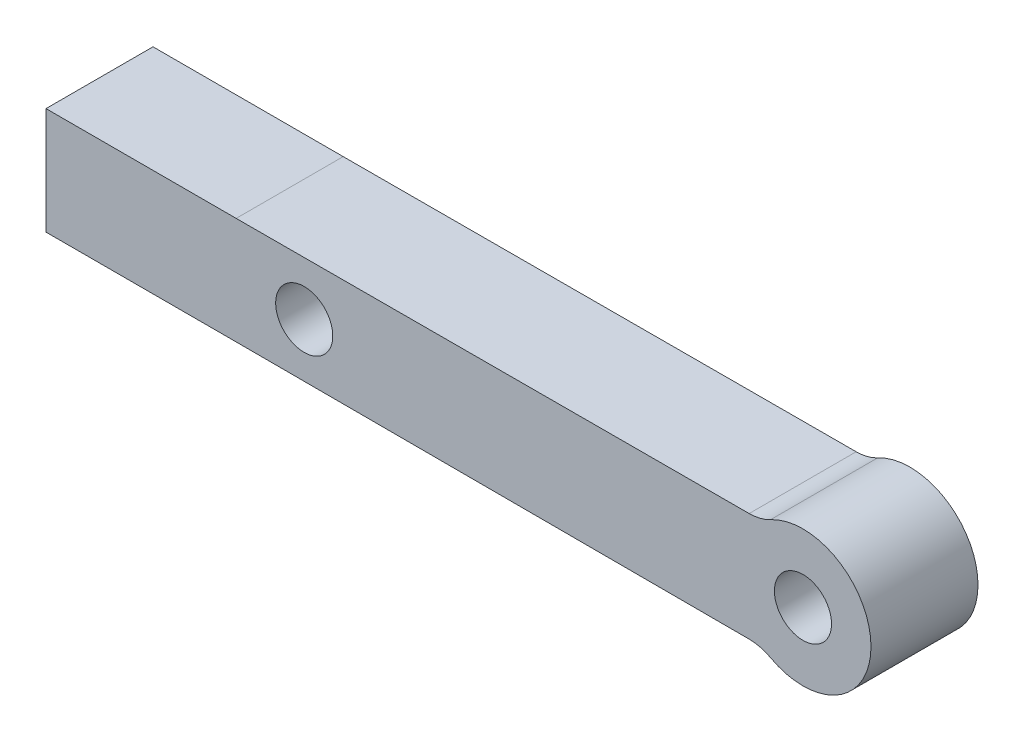
SolidWorks part; units mm, degrees
ref_plane "Front Plane" through (0, 0, 0) normal (0, 0, 1) x (1, 0, 0)
ref_plane "Top Plane" through (0, 0, 0) normal (0, 1, 0) x (1, 0, 0)
ref_plane "Right Plane" through (0, 0, 0) normal (1, 0, 0) x (0, 0, -1)
sketch "Sketch1" plane through (0, 0, 0) normal (0, 0, 1) x (1, 0, 0)
  line L0 (-31.75, 2.9972) -> (-37.7444, 2.9972)
  line L1 (-37.7444, 2.9972) -> (-42.4037, 2.9972)
  line L2 (-31.75, 2.9972) -> (-3.014, 3.0467)
  line L3 (-42.4037, 2.9972) -> (-42.4037, -2.9972)
  line L4 (-31.75, -2.9972) -> (-3.014, -3.0467)
  line L6 (-37.7444, -2.9972) -> (-31.75, -2.9972)
  line L7 (-42.4037, -2.9972) -> (-37.7444, -2.9972)
  circle A0 centre (0, 0) radius 1.6
  arc A1 (-1.811, -3.352) -> (-1.811, 3.352) centre (0, 0) ccw
  arc A2 (-1.811, 3.352) -> (-3.014, 3.0467) centre (-3.0184, 5.5867) cw
  arc A3 (-1.811, -3.352) -> (-3.014, -3.0467) centre (-3.0184, -5.5867) ccw
  circle A4 centre (-27.94, 0) radius 1.6
  point P17 (-31.75, 0)
  dimension "D1" = 2.54
  dimension "D2" = 2.54
extrude "Boss-Extrude1" add sketch "Sketch1" along normal blind 5.9944
